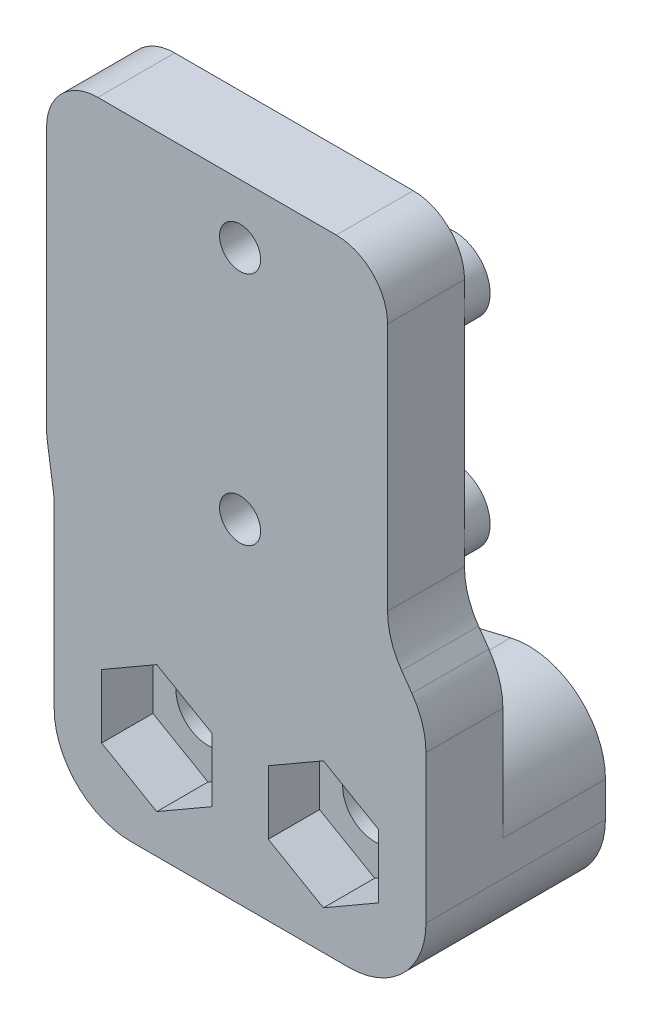
SolidWorks part; units mm, degrees
ref_plane "Front Plane" through (0, 0, 0) normal (0, 0, 1) x (1, 0, 0)
ref_plane "Top Plane" through (0, 0, 0) normal (0, 1, 0) x (1, 0, 0)
ref_plane "Right Plane" through (0, 0, 0) normal (1, 0, 0) x (0, 0, -1)
sketch "草图1" plane through (0, 0, 0) normal (0, 0, 1) x (1, 0, 0)
  line L0 (-26.8611, 10.2702) -> (-12.3611, 10.2702)
  line L6 (-26.8611, 20.3576) -> (-26.8611, 10.2702)
  line L10 (-12.3611, 10.2702) -> (-12.3611, 19.9795)
  line L15 (-25.7592, 31.7878) -> (-25.7592, 23.9878) construction
  line L16 (-25.7592, 23.9878) -> (-15.2592, 23.9878) construction
  line L17 (-15.2592, 23.9878) -> (-15.2592, 31.7878) construction
  line L18 (-15.2592, 31.7878) -> (-25.7592, 31.7878) construction
  line L19 (-25.7592, 31.7878) -> (-15.2592, 23.9878) construction
  line L20 (-15.2592, 31.7878) -> (-25.7592, 23.9878) construction
  line L21 (-16.3611, 14.2702) -> (-22.8611, 14.2702) construction
  line L24 (-19.6111, 27.8878) -> (-19.6111, 14.2702) construction
  line L25 (-16.6456, 27.8878) -> (-23.2139, 27.8878) construction
  line L26 (-27.1592, 34.7618) -> (-13.8592, 34.7618)
  line L31 (-13.8592, 34.7618) -> (-13.8592, 22.106)
  line L32 (-27.1592, 34.7618) -> (-27.1592, 22.3757)
  line L33 (-27.1592, 22.3757) -> (-26.8611, 20.3576)
  line L34 (-13.8592, 22.106) -> (-12.3611, 19.9795)
  circle A17 centre (-16.3611, 14.2702) radius 1.25
  circle A18 centre (-22.8611, 14.2702) radius 1.25
  circle A20 centre (-25.7592, 31.7878) radius 1.4
  circle A21 centre (-25.7592, 23.9878) radius 1.4
  circle A22 centre (-15.2592, 23.9878) radius 1.4
  circle A23 centre (-19.6111, 27.8878) radius 14 construction
  circle A26 centre (-15.2592, 31.7878) radius 1.4
  circle A27 centre (-19.6111, 32.4581) radius 0.8
  circle A28 centre (-19.6111, 23.2847) radius 0.8
  point P1 (-19.6111, 27.8878)
  point P12 (-20.5092, 27.8878)
  point P26 (-20.5092, 27.8878)
  dimension "D5" = 2.5
  dimension "D6" = 2.5
  dimension "D4" = 4
  dimension "D8" = 1.6
  dimension "D9" = 2.8
  dimension "D2" = 1.6
  dimension "D10" = 2.8
  dimension "D3" = 4
  dimension "D7" = 2.8
  dimension "D13" = 28
  dimension "D15" = 7.8
  dimension "D12" = 10.5
  dimension "D11" = 4
  dimension "D14" = 6.5
extrude "凸台-拉伸1" add sketch "草图1" along normal blind 3 contours A17 | A18 | A27 | A28 | L26 L31 L34 L10 L0 L6 L33 L32
extrude "凸台-拉伸2" add sketch "草图1<3>" against normal blind 1 contours A20 | A21 | A22 | A26
sketch "草图1<3>" plane through (0, 0, 0) normal (0, 0, 1) x (1, 0, 0) same geometry as "草图1"
sketch "草图2" plane through (0, 0, 0) normal (0, 0, -1) x (-1, 0, 0)
  line L0 (12.3611, 10.2702) -> (12.3611, 19.9795) construction
  line L2 (12.3611, 18.4402) -> (12.3611, 10.2702)
  line L3 (12.3611, 10.2702) -> (26.8611, 10.2702)
  line L4 (26.8611, 14.6396) -> (26.8611, 10.2702)
  line L5 (26.8611, 20.3576) -> (26.8611, 10.2702) construction
  line L7 (23.7621, 16.5482) -> (26.8611, 14.6396)
  line L8 (23.7621, 16.5482) -> (19.1649, 16.8137)
  line L9 (19.1649, 16.8137) -> (12.3611, 18.4402)
  circle A0 centre (16.3611, 14.2702) radius 1.25
  circle A1 centre (22.8611, 14.2702) radius 1.25
  point P4 (19.6111, 13.64)
extrude "凸台-拉伸4" add sketch "草图2" along normal blind 4
fillet "圆角4" radius 2 2 edges at (-27.1592, 34.7618, 1.5) (-13.8592, 34.7618, 1.5)
fillet "圆角5" radius 3 10 edges at (-27.1592, 22.3757, 1.5) (-26.8611, 20.3576, 1.5) (-19.1649, 16.8137, -2) (-23.7621, 16.5482, -2) (-26.8611, 10.2702, -0.5) (-26.8611, 14.6396, -2) (-12.3611, 10.2702, -0.5) (-12.3611, 18.4402, -2) (-13.8592, 22.106, 1.5) (-12.3611, 19.9795, 1.5)
sketch "草图3" plane through (0, 0, 3) normal (0, 0, 1) x (1, 0, 0)
  line L0 (-22.8611, 16.7528) -> (-20.7111, 15.5115)
  line L1 (-20.7111, 15.5115) -> (-20.7111, 13.0289)
  line L2 (-20.7111, 13.0289) -> (-22.8611, 11.7876)
  line L3 (-22.8611, 11.7876) -> (-25.0111, 13.0289)
  line L4 (-25.0111, 13.0289) -> (-25.0111, 15.5115)
  line L5 (-25.0111, 15.5115) -> (-22.8611, 16.7528)
  line L6 (-22.8611, 16.7528) -> (-22.8611, 11.7876) construction
  line L7 (-25.0111, 15.5115) -> (-20.7111, 13.0289) construction
  line L8 (-16.3611, 16.7528) -> (-14.2111, 15.5115)
  line L9 (-14.2111, 15.5115) -> (-14.2111, 13.0289)
  line L10 (-14.2111, 13.0289) -> (-16.3611, 11.7876)
  line L11 (-16.3611, 11.7876) -> (-18.5111, 13.0289)
  line L12 (-18.5111, 13.0289) -> (-18.5111, 15.5115)
  line L13 (-18.5111, 15.5115) -> (-16.3611, 16.7528)
  line L14 (-16.3611, 16.7528) -> (-16.3611, 11.7876) construction
  line L15 (-18.5111, 15.5115) -> (-14.2111, 13.0289) construction
  point P2 (-16.3611, 14.2702)
  point P7 (-22.8611, 14.2702)
  point P17 (-16.3611, 14.2702)
  dimension "D1" = 120
  dimension "D2" = 240
  dimension "D3" = 4.3
  dimension "D4" = 120
  dimension "D5" = 240
  dimension "D6" = 4.3
extrude "切除-拉伸1" cut sketch "草图3" against normal blind 2
